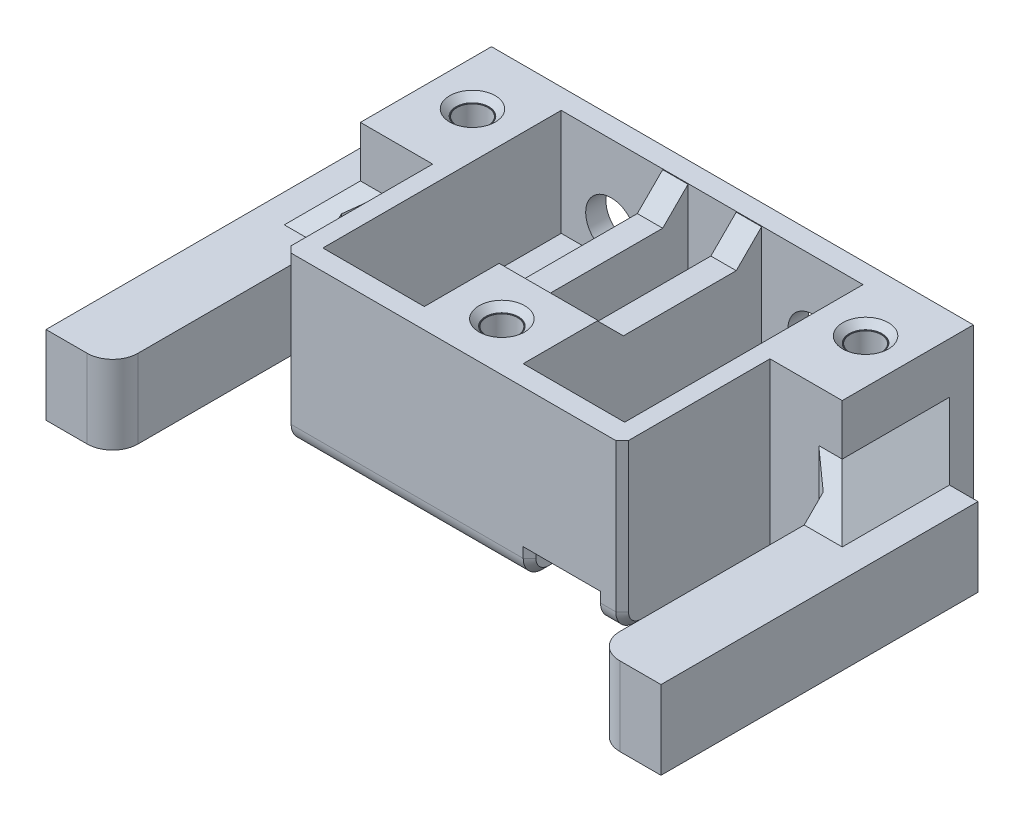
SolidWorks part; units mm, degrees
ref_plane "Front Plane" through (0, 0, 0) normal (0, 0, 1) x (1, 0, 0)
ref_plane "Top Plane" through (0, 0, 0) normal (0, 1, 0) x (1, 0, 0)
ref_plane "Right Plane" through (0, 0, 0) normal (1, 0, 0) x (0, 0, -1)
sketch "Sketch1" plane through (0, 0, 0) normal (0, 1, 0) x (1, 0, 0)
  line L1 (13.5, -11) -> (-13.5, -11)
  line L2 (13.5, -11) -> (13.5, 11)
  line L3 (13.5, 11) -> (-13.5, 11)
  line L4 (-13.5, -11) -> (-13.5, 11)
  line L5 (13.5, -11) -> (-13.5, 11) construction
  line L6 (13.5, 11) -> (-13.5, -11) construction
  point P0 (0, 0)
  dimension "D1" = 27
  dimension "D2" = 22
extrude "Boss-Extrude1" add sketch "Sketch1" along normal blind 12
shell "Shell1" thickness 1.6 removed face at (0, 12, 0)
sketch "Sketch2" plane through (0, 1.6, 0) normal (0, 1, 0) x (1, 0, 0)
  line L0 (-11.9, -9.4) -> (11.9, -9.4) construction
  line L4 (-3.9, 9.4) -> (-3.9, -9.4)
  line L5 (-1.9, 9.4) -> (-1.9, -9.4)
  line L6 (11.9, 9.4) -> (-11.9, 9.4) construction
  line L7 (-1.9, -9.4) -> (-3.9, -9.4)
  line L8 (-1.9, 9.4) -> (-3.9, 9.4)
  line L9 (-11.9, 9.4) -> (-11.9, -9.4) construction
  dimension "D1" = 8
  dimension "D2" = 2
extrude "Boss-Extrude2" add sketch "Sketch2" along normal up to surface (10.4 mm away) up to face at (0, 12, 0)
sketch "Sketch3" plane through (0, 12, 0) normal (0, 1, 0) x (1, 0, 0)
  line L0 (-11.9, -9.4) -> (-3.9, -9.4) construction
  line L1 (-11.9, -9.4) -> (-10.9, -9.4)
  line L2 (-11.9, -9.4) -> (-11.9, -11)
  line L3 (-11.9, -11) -> (-10.9, -11)
  line L4 (-10.9, -9.4) -> (-10.9, -11)
  line L5 (-13.5, -11) -> (13.5, -11) construction
  line L6 (-13.5, 11) -> (-13.5, -11) construction
  point P8 (-11.4, -11)
  dimension "D1" = 1
  dimension "D2" = 2.1
extrude "Cut-Extrude1" [suppressed] cut sketch "Sketch3" against normal blind 7.5
sketch "Sketch4" plane through (0, 0, -11) normal (0, 0, -1) x (-1, 0, 0)
  line L0 (16.436, 0) -> (-16.436, 0) construction
  circle A0 centre (7.9737, 6) radius 2
  dimension "D1" = 6
extrude "Cut-Extrude2" cut sketch "Sketch4" against normal blind 9
ref_plane "Mirror Plane" through (0, 0, 0) normal (-1, 0, 0) x (0, 0, 1)
sketch "Sketch6" plane through (-13.5, 0, 0) normal (-1, 0, 0) x (0, 0, 1)
  line L0 (-11, 12) -> (11, 12) construction
  line L1 (-0.66, 12) -> (-11, 12)
  line L2 (-0.66, 12) -> (-0.66, 0)
  line L3 (-0.66, 0) -> (-11, 0)
  line L4 (-11, 12) -> (-11, 0)
  dimension "D1" = 10.34
extrude "Boss-Extrude4" add sketch "Sketch6" along normal blind 5.5
sketch "Sketch7" plane through (-19, 0, 0) normal (-1, 0, 0) x (0, 0, 1)
  line L0 (-0.66, 12) -> (-11, 12) construction
  line L1 (-6.1164, 5) -> (18.8836, 5)
  line L2 (-6.1164, 5) -> (-6.1164, 0)
  line L3 (-6.1164, 0) -> (18.8836, 0)
  line L4 (18.8836, 5) -> (18.8836, 0)
  line L6 (-11, 0) -> (-0.66, 0) construction
  dimension "D1" = 25
  dimension "D3" = 7
extrude "Boss-Extrude5" add sketch "Sketch7" along normal blind 5.25
chamfer "Chamfer1" distance 3 angle 45 1 edges at (-19, 2.5, -6.1164)
sketch "Sketch8" plane through (0, 12, 0) normal (0, 1, 0) x (1, 0, 0)
  line L0 (13.5, 11) -> (-19, 11) construction
  line L1 (0, 6.413) -> (0, -6.413) construction
  circle A0 centre (-15.5, 6) radius 2
  dimension "D1" = 5
  dimension "D2" = 15.5
extrude "Cut-Extrude3" cut sketch "Sketch8" against normal through all
chamfer "Chamfer2" distance 1.5 angle 51 1 edges at (-19, 2.5, -0.66) first distance on face at (-19, 2.5, 9.1118)
chamfer "Chamfer3" [suppressed] distance 2 angle 50
fillet "Fillet1" radius 2 1 edges at (-19, 2.5, 18.8836)
mirror "Mirror1" about plane through (0, 0, 0) normal (-1, 0, 0) of "Boss-Extrude2", "Cut-Extrude1", "Cut-Extrude2", "Boss-Extrude4", "Boss-Extrude5", "Chamfer1", "Cut-Extrude3", "Chamfer2", "Chamfer3", "Fillet1"
sketch "Sketch10" [suppressed] plane through (0, 1.6, 0) normal (0, 1, 0) x (1, 0, 0)
  line L0 (1.9, -9.4) -> (1.9, 9.4) construction
  line L1 (-1.9, -9.4) -> (1.9, -9.4)
  line L2 (-1.9, -9.4) -> (-1.9, -3.4)
  line L3 (-1.9, -3.4) -> (1.9, -3.4)
  line L4 (1.9, -9.4) -> (1.9, -3.4)
  dimension "D1" = 6
extrude "Boss-Extrude6" [suppressed] add sketch "Sketch10" along normal up to surface (10.4 mm away) up to face at (15.5, 12, -4)
sketch "Sketch12" plane through (0, 0, 0) normal (0, -1, 0) x (1, 0, 0)
  line L0 (6.6, 11) -> (-13.5, 11)
  line L2 (6.6, -11) -> (6.6, 11)
  line L4 (11.1, -11) -> (11.1, 11)
  line L5 (11.1, -11) -> (19, -11)
  line L20 (24.25, 18.8836) -> (21, 18.8836)
  line L21 (19, 16.8836) -> (19, 0.84)
  line L22 (19, 0.84) -> (17.1477, -0.66)
  line L23 (17.1477, -0.66) -> (13.5, -0.66)
  line L24 (13.5, -0.66) -> (13.5, 11)
  line L25 (13.5, 11) -> (-13.5, 11)
  line L26 (-13.5, 11) -> (-13.5, -0.66)
  line L27 (-13.5, -0.66) -> (-17.1477, -0.66)
  line L28 (-17.1477, -0.66) -> (-19, 0.84)
  line L29 (-19, 0.84) -> (-19, 16.8836)
  line L30 (-21, 18.8836) -> (-24.25, 18.8836)
  line L31 (-24.25, 18.8836) -> (-24.25, -6.1164)
  line L32 (-24.25, -6.1164) -> (-22, -6.1164)
  line L33 (-22, -6.1164) -> (-19, -9.1164)
  line L34 (-19, -9.1164) -> (-19, -11)
  line L35 (-19, -11) -> (19, -11)
  line L36 (19, -11) -> (19, -9.1164)
  line L37 (19, -9.1164) -> (22, -6.1164)
  line L38 (22, -6.1164) -> (24.25, -6.1164)
  line L39 (24.25, -6.1164) -> (24.25, 18.8836)
  line L40 (24.25, 18.8836) -> (21, 18.8836)
  line L41 (19, 16.8836) -> (19, 0.84)
  line L42 (19, 0.84) -> (17.1477, -0.66)
  line L43 (17.1477, -0.66) -> (13.5, -0.66)
  line L44 (13.5, -0.66) -> (13.5, 11)
  line L45 (13.5, 11) -> (11.1, 11)
  line L46 (-13.5, 11) -> (-13.5, -0.66)
  line L47 (-13.5, -0.66) -> (-17.1477, -0.66)
  line L48 (-17.1477, -0.66) -> (-19, 0.84)
  line L49 (-19, 0.84) -> (-19, 16.8836)
  line L50 (-21, 18.8836) -> (-24.25, 18.8836)
  line L51 (-24.25, 18.8836) -> (-24.25, -6.1164)
  line L52 (-24.25, -6.1164) -> (-22, -6.1164)
  line L53 (-22, -6.1164) -> (-19, -9.1164)
  line L54 (-19, -9.1164) -> (-19, -11)
  line L55 (-19, -11) -> (6.6, -11)
  line L56 (19, -11) -> (19, -9.1164)
  line L57 (19, -9.1164) -> (22, -6.1164)
  line L58 (22, -6.1164) -> (24.25, -6.1164)
  line L59 (24.25, -6.1164) -> (24.25, 18.8836)
  arc A2 (21, 18.8836) -> (19, 16.8836) centre (21, 16.8836) ccw
  arc A3 (-19, 16.8836) -> (-21, 18.8836) centre (-21, 16.8836) ccw
  arc A4 (21, 18.8836) -> (19, 16.8836) centre (21, 16.8836) ccw
  arc A5 (-19, 16.8836) -> (-21, 18.8836) centre (-21, 16.8836) ccw
  dimension "D2" = 4.5
  dimension "D4" = 7.9
  dimension "D1" = 0
extrude "Boss-Extrude7" add sketch "Sketch12" along normal blind 1.2
sketch "Sketch13" plane through (0, 0, 0) normal (0, -1, 0) x (-1, 0, 0)
  line L1 (-6.6, -11) -> (-11.1, -11)
  line L2 (-6.6, -11) -> (-6.6, 11)
  line L3 (-6.6, 11) -> (-11.1, 11)
  line L4 (-11.1, -11) -> (-11.1, 11)
extrude "Cut-Extrude5" cut sketch "Sketch13" against normal blind 1
sketch "Sketch14" [suppressed] plane through (0, 12, 0) normal (0, 1, 0) x (1, 0, 0)
  line L1 (-1.9, 9.4) -> (1.9, 9.4)
  line L2 (-1.9, 9.4) -> (-1.9, -3.4)
  line L3 (-1.9, -3.4) -> (1.9, -3.4)
  line L4 (1.9, 9.4) -> (1.9, -3.4)
  line L21 (-13.5, -11) -> (13.5, -11)
  line L22 (13.5, -11) -> (13.5, 0.66)
  line L23 (13.5, 0.66) -> (19, 0.66)
  line L24 (19, 0.66) -> (19, 11)
  line L25 (19, 11) -> (-19, 11)
  line L26 (-19, 11) -> (-19, 0.66)
  line L27 (-19, 0.66) -> (-13.5, 0.66)
  line L28 (-13.5, 0.66) -> (-13.5, -11)
  line L41 (-13.5, -11) -> (13.5, -11)
  line L42 (13.5, -11) -> (13.5, 0.66)
  line L43 (13.5, 0.66) -> (19, 0.66)
  line L44 (19, 0.66) -> (19, 11)
  line L45 (19, 11) -> (-19, 11)
  line L46 (-19, 11) -> (-19, 0.66)
  line L47 (-19, 0.66) -> (-13.5, 0.66)
  line L48 (-13.5, 0.66) -> (-13.5, -11)
  circle A0 centre (-15.5, 6) radius 1.6
  circle A1 centre (15.5, 6) radius 1.6
  circle A2 centre (0, -7.1811) radius 1.6
  dimension "D1" = 0
sketch "Sketch16" [suppressed] plane through (13.5, 0, 0) normal (1, 0, 0) x (0, 0, -1)
  line L1 (0.66, -1.2) -> (-11, -1.2)
  line L2 (0.66, -1.2) -> (0.66, 12)
  line L3 (0.66, 12) -> (-11, 12)
  line L4 (-11, -1.2) -> (-11, 12)
sketch "Sketch17" plane through (-13.5, 0, 0) normal (-1, 0, 0) x (0, 0, 1)
  line L1 (-0.66, 12) -> (11, 12)
  line L2 (-0.66, 12) -> (-0.66, -1.2)
  line L3 (-0.66, -1.2) -> (11, -1.2)
  line L4 (11, 12) -> (11, -1.2)
extrude "Cut- tolerance fix" cut sketch "Sketch17" against normal blind 0.2
mirror "Mirror2" about plane through (0, 0, 0) normal (-1, 0, 0) of "Cut- tolerance fix"
fillet "Fillet2" radius 1.5 2 edges at (12.2, -1.2, 11) (-3.35, -1.2, 11)
sketch "Sketch18" plane through (0, 1.6, 0) normal (0, 1, 0) x (1, 0, 0)
  line L0 (-1.9, -9.4) -> (-1.9, 9.4) construction
  line L1 (1.9, -9.4) -> (-1.9, -9.4)
  line L2 (1.9, -9.4) -> (1.9, -3.5)
  line L3 (1.9, -3.5) -> (-1.9, -3.5)
  line L4 (-1.9, -9.4) -> (-1.9, -3.5)
  line L5 (-13.3, -11) -> (13.3, -11) construction
  dimension "D1" = 7.5
extrude "Boss-Extrude8" add sketch "Sketch18" along normal up to surface (10.4 mm away) up to face at (15.5, 12, -4)
sketch "Sketch11" plane through (0, 12, 0) normal (0, 1, 0) x (1, 0, 0)
  circle A0 centre (0, -7.1811) radius 2
extrude "Cut-Extrude6" cut sketch "Sketch11" against normal blind 10
sketch "Sketch19" plane through (0, 1.6, 0) normal (0, 1, 0) x (1, 0, 0)
  line L0 (3.9, 9.4) -> (3.9, -9.4) construction
  line L1 (3.9, -9.4) -> (11.9, -9.4) construction
  line L2 (11.9, -9.4) -> (11.9, 9.4) construction
  line L3 (11.9, 9.4) -> (3.9, 9.4) construction
  line L4 (-11.9, -9.4) -> (-3.9, -9.4) construction
  line L5 (-3.9, -9.4) -> (-3.9, 9.4) construction
  line L6 (-3.9, 9.4) -> (-11.9, 9.4) construction
  line L7 (-11.9, 9.4) -> (-11.9, -9.4) construction
  line L8 (3.9, 9.4) -> (3.9, -9.4)
  line L9 (3.9, -9.4) -> (11.9, -9.4)
  line L10 (11.9, -9.4) -> (11.9, 9.4)
  line L11 (11.9, 9.4) -> (3.9, 9.4)
  line L12 (-11.9, -9.4) -> (-3.9, -9.4)
  line L13 (-3.9, -9.4) -> (-3.9, 9.4)
  line L14 (-3.9, 9.4) -> (-11.9, 9.4)
  line L15 (-11.9, 9.4) -> (-11.9, -9.4)
extrude "Boss-Extrude9" add sketch "Sketch19" along normal blind 2
sketch "Sketch20" plane through (0, 1, 0) normal (0, -1, 0) x (1, 0, 0)
  line L4 (6.6, 11) -> (6.6, -11)
  line L5 (6.6, -11) -> (11.1, -11)
  line L6 (11.1, -11) -> (11.1, 11)
  line L7 (11.1, 11) -> (6.6, 11)
  line L8 (6.6, 11) -> (6.6, -11)
  line L9 (6.6, -11) -> (11.1, -11)
  line L10 (11.1, -11) -> (11.1, 11)
  line L11 (11.1, 11) -> (6.6, 11)
  dimension "D1" = 0
extrude "Cut-Extrude7" cut sketch "Sketch20" against normal blind 0.1
sketch "Sketch21" plane through (0, 12, 0) normal (0, 1, 0) x (1, 0, 0)
  line L0 (1.9, -3.5) -> (-1.9, -3.5) construction
  line L1 (3.9, -3.5) -> (-3.9, -3.5)
  line L2 (3.9, -3.5) -> (3.9, 9.4)
  line L3 (3.9, 9.4) -> (-3.9, 9.4)
  line L4 (-3.9, -3.5) -> (-3.9, 9.4)
  line L5 (3.9, -3.5) -> (-3.9, 9.4) construction
  line L6 (3.9, 9.4) -> (-3.9, -3.5) construction
  point P0 (0, 2.95)
extrude "Cut-Extrude8" cut sketch "Sketch21" against normal blind 2.05
chamfer "Chamfer4" distance 2 angle 45 4 edges at (2.9, 9.95, 3.5) (-2.9, 9.95, 3.5) (2.9, 9.95, -9.4) (-2.9, 9.95, -9.4)
chamfer "Chamfer5" distance 3 angle 45 4 edges at (-18.0738, 5, -0.66) (-19, 5, -4.8882) (18.0738, 5, -0.66) (19, 5, -4.8882)
sketch "Sketch22" plane through (6.6, 0, 0) normal (1, 0, 0) x (0, 0, -1)
  line L4 (-11, 1.1) -> (-11, 0.3)
  line L5 (-9.5, -1.2) -> (11, -1.2)
  line L6 (11, -1.2) -> (11, 1.1)
  line L7 (11, 1.1) -> (-11, 1.1)
  line L8 (-11, 1.1) -> (-11, 0.3)
  line L9 (-9.5, -1.2) -> (11, -1.2)
  line L10 (11, -1.2) -> (11, 1.1)
  line L11 (11, 1.1) -> (-11, 1.1)
  arc A1 (-11, 0.3) -> (-9.5, -1.2) centre (-9.5, 0.3) ccw
  arc A2 (-11, 0.3) -> (-9.5, -1.2) centre (-9.5, 0.3) ccw
  dimension "D1" = 0
extrude "tolerance adj" cut sketch "Sketch22" against normal blind 0.6
chamfer "Chamfer6" distance 0.5 angle 45 12 edges at (-13.3, 6.15, 11) (-13.3, -0.7607, 10.5607) (-13.3, -1.2, 4.42) (13.3, 6.15, 11) (13.3, -0.7607, 10.5607) (13.3, -1.2, 4.42) (6, -1.2, -0.75) (6, -0.7607, 10.5607) (6, 0.7, 11) (11.1, 0.7, 11) (11.1, -0.7607, 10.5607) (11.1, -1.2, -0.75)
sketch "Sketch23" plane through (0, 2, 0) normal (0, 1, 0) x (1, 0, 0)
  circle A1 centre (-15.5, 6) radius 2
  circle A2 centre (-15.5, 6) radius 2
  circle A3 centre (15.5, 6) radius 2
  circle A4 centre (15.5, 6) radius 2
  circle A5 centre (0, -7.1811) radius 2
  circle A6 centre (0, -7.1811) radius 2
  dimension "D1" = 0
  dimension "D2" = 0
  dimension "D3" = 0
extrude "Boss-Extrude10" add sketch "Sketch23" along normal blind 9.5
sketch "Sketch24" plane through (0, 11.5, 0) normal (0, 1, 0) x (1, 0, 0)
  point P0 (0, -7.1811)
  point P3 (-15.5, 6)
  point P6 (15.5, 6)
hole_wizard "Ø2.45 (2.45) Diameter Hole1" positions "Sketch24" profile "Sketch25" hole size "Ø2.45" standard "ANSI Metric"
sketch "Sketch25" plane through (0, 11.5, 7.1811) normal (1, 0, 0) x (0, 0, 1)
  line L0 (0, 0) -> (0, 10.7361)
  line L1 (0, 10.7361) -> (1.225, 10)
  line L2 (1.225, 10) -> (1.225, 0.025)
  line L3 (1.225, 0.025) -> (1.25, 0)
  line L5 (1.25, 0) -> (0, 0)
  line L6 (-1.225, 0.025) -> (-1.25, 0) construction
  line L10 (0, 10.7361) -> (-1.225, 10) construction
  line L11 (0, -6.35) -> (0, 107.95) construction
  dimension "Hole Dia." = 2.45
  dimension "Hole Depth" = 10
  dimension "Near C'Sink Dia." = 2.5
  dimension "Near C'Sink Angle" = 90
  dimension "Drill Angle" = 118
chamfer "Chamfer7" distance 0.7 angle 45 3 edges at (15.5, 11.5, -4) (0, 11.5, 9.1811) (-15.5, 11.5, -4)
